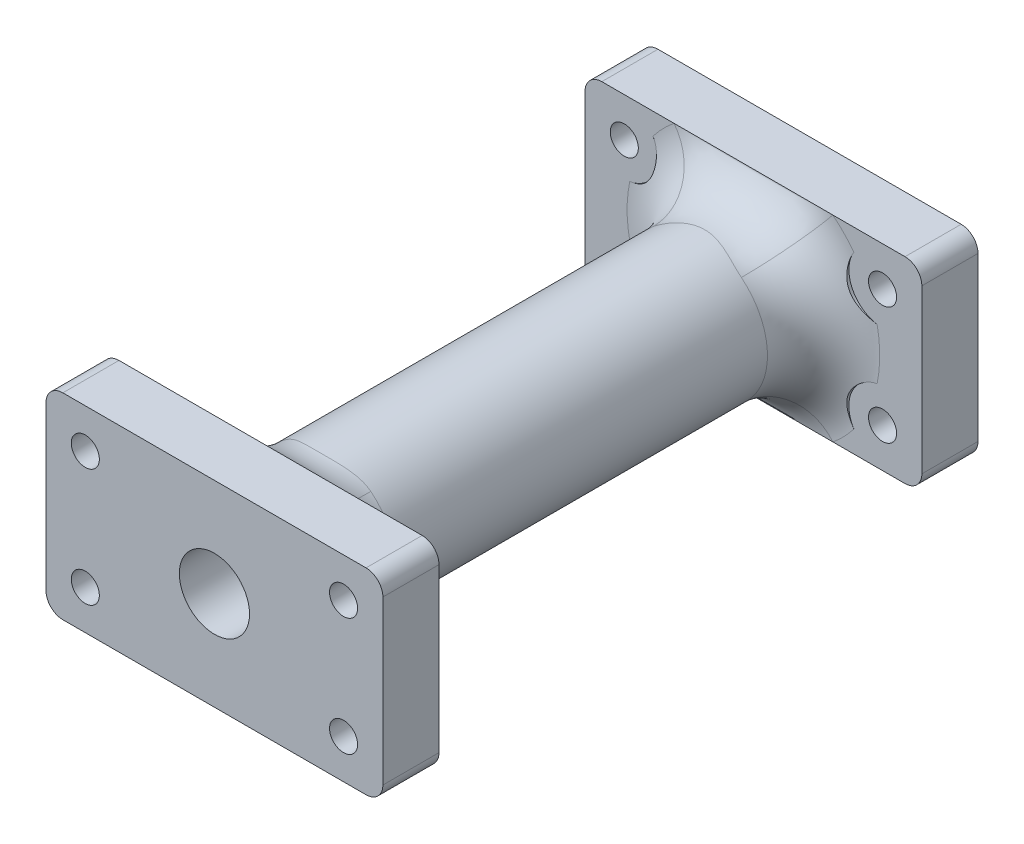
SolidWorks part; units mm, degrees
ref_plane "Front Plane" through (0, 0, 0) normal (0, 0, 1) x (1, 0, 0)
ref_plane "Top Plane" through (0, 0, 0) normal (0, 1, 0) x (1, 0, 0)
ref_plane "Right Plane" through (0, 0, 0) normal (1, 0, 0) x (0, 0, -1)
sketch "Sketch1" plane through (0, 0, 0) normal (0, 0, 1) x (1, 0, 0)
  line L1 (-53, 29) -> (-7, 29) construction
  line L2 (-53, 29) -> (-53, 50) construction
  line L3 (-53, 50) -> (-7, 50) construction
  line L4 (-7, 29) -> (-7, 50) construction
  line L5 (-53, 29) -> (-7, 50) construction
  line L6 (-53, 50) -> (-7, 29) construction
  point P0 (-30, 39.5)
sketch "Sketch2" plane through (0, 0, 0) normal (0, 0, 1) x (1, 0, 0)
  line L0 (-53, 29) -> (-7, 50) construction
  line L1 (0, 22) -> (-60, 22)
  line L2 (0, 22) -> (0, 57)
  line L3 (0, 57) -> (-60, 57)
  line L4 (-60, 22) -> (-60, 57)
  line L5 (0, 22) -> (-60, 57) construction
  line L6 (0, 57) -> (-60, 22) construction
  circle A0 centre (-30, 39.5) radius 6.25
  point P0 (-30, 39.5)
  dimension "D1" = 12.5
  dimension "D2" = 60
  dimension "D3" = 35
extrude "Boss-Extrude1" add sketch "Sketch2" along normal blind 10
hole_wizard "Ø5.0 (5) Diameter Hole1" positions "Sketch3" profile "Sketch4" hole size "Ø5.0" standard "ISO" end condition through all
sketch "Sketch3" plane through (0, 0, 10) normal (0, 0, 1) x (1, 0, 0)
  point P0 (-53, 50)
  point P3 (-7, 50)
  point P6 (-7, 29)
  point P9 (-53, 29)
sketch "Sketch4" plane through (-53, 50, 10) normal (1, 0, 0) x (0, -1, 0)
  line L0 (0, 0) -> (0, 10)
  line L1 (0, 10) -> (2.5, 10)
  line L2 (2.5, 10) -> (2.5, 0)
  line L5 (2.5, 0) -> (0, 0)
  line L11 (0, -6.35) -> (0, 107.95) construction
  dimension "Thru Hole Dia." = 5
  dimension "Thru Hole Depth" = 10
sketch "Sketch5" plane through (0, 0, 10) normal (0, 0, 1) x (1, 0, 0)
  line L0 (-53, 50) -> (-7, 29) construction
  circle A0 centre (-30, 39.5) radius 12.5
  circle A1 centre (-30, 39.5) radius 6.25
  circle A2 centre (-30, 39.5) radius 6.25 construction
  dimension "D1" = 25
extrude "Boss-Extrude2" add sketch "Sketch5" along normal blind 86
ref_plane "Plane1" through (0, 0, 53) normal (0, 0, 1) x (1, 0, 0)
mirror "Mirror1" about plane through (0, 0, 53) normal (0, 0, 1) of "Boss-Extrude1"
fillet "Fillet1" radius 10 2 edges at (-17.5, 39.5, 96) (-17.5, 39.5, 10)
hole_wizard "Ø5.0 (5) Diameter Hole2" positions "Sketch6" profile "Sketch7" hole size "Ø5.0" standard "ISO" end condition through all
sketch "Sketch6" plane through (0, 0, 96) normal (0, 0, -1) x (-1, 0, 0)
  point P0 (7, 50)
  point P3 (53, 50)
  point P6 (53, 29)
  point P9 (7, 29)
sketch "Sketch7" plane through (-7, 50, 96) normal (1, 0, 0) x (0, 1, 0)
  line L0 (0, 0) -> (0, 10)
  line L1 (0, 10) -> (2.5, 10)
  line L2 (2.5, 10) -> (2.5, 0)
  line L5 (2.5, 0) -> (0, 0)
  line L11 (0, -6.35) -> (0, 107.95) construction
  dimension "Thru Hole Dia." = 5
  dimension "Thru Hole Depth" = 10
sketch "Sketch11" plane through (0, 0, 10) normal (0, 0, 1) x (1, 0, 0)
  circle A0 centre (-53, 50) radius 6
  circle A1 centre (-53, 29) radius 6
  circle A2 centre (-7, 29) radius 6
  circle A3 centre (-7, 50) radius 6
  dimension "D1" = 12
extrude "Cut-Extrude1" cut sketch "Sketch11" along normal blind 28
mirror "Mirror2" about plane through (0, 0, 53) normal (0, 0, 1) of "Cut-Extrude1"
fillet "Fillet2" radius 3 8 edges at (0, 57, 101) (0, 22, 101) (-60, 22, 101) (-60, 57, 101) (0, 57, 5) (0, 22, 5) (-60, 22, 5) (-60, 57, 5)
